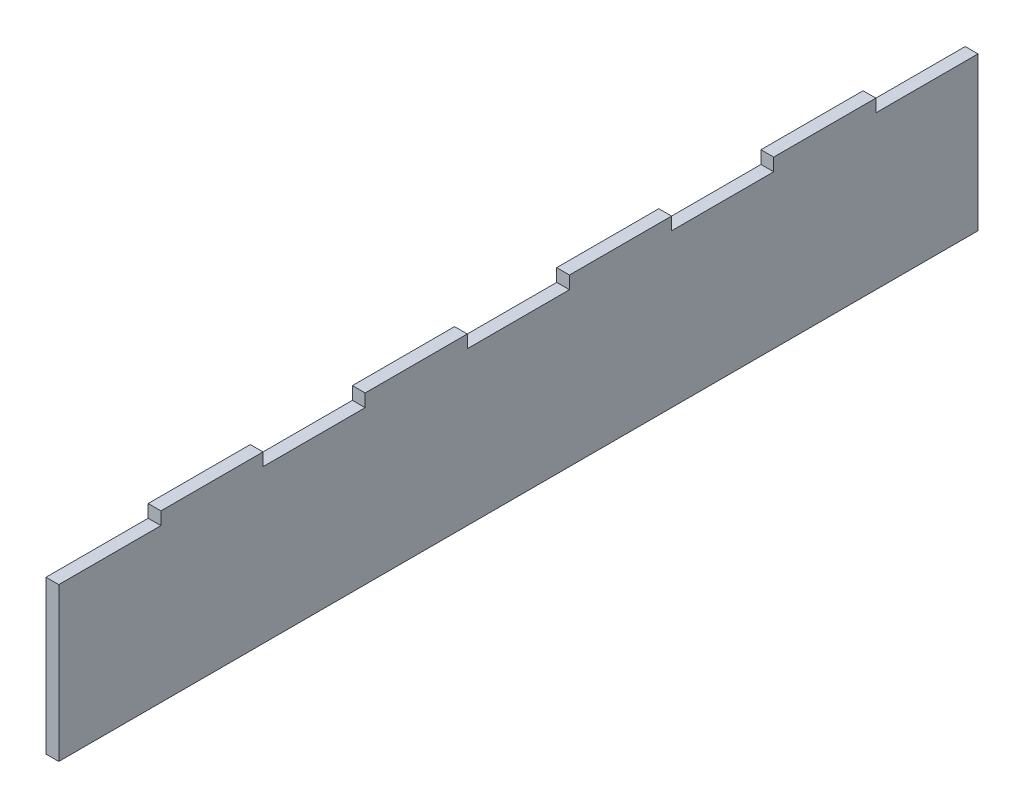
SolidWorks part; units mm, degrees
material "Pine"
ref_plane "Front Plane" through (0, 0, 0) normal (0, 0, 1) x (1, 0, 0)
ref_plane "Top Plane" through (0, 0, 0) normal (0, 1, 0) x (1, 0, 0)
ref_plane "Right Plane" through (0, 0, 0) normal (1, 0, 0) x (0, 0, -1)
sketch "Sketch1" plane through (0, 0, 0) normal (0, 0, 1) x (1, 0, 0)
  line L1 (-38.1, -38.1) -> (-44.45, -38.1)
  line L2 (-38.1, -38.1) -> (-38.1, 38.1)
  line L3 (-38.1, 38.1) -> (-44.45, 38.1)
  line L4 (-44.45, -38.1) -> (-44.45, 38.1)
extrude "Boss-Extrude1" add sketch "Sketch1" against normal up to surface (457.2 mm away)
sketch "Sketch2" plane through (0, 38.1, 0) normal (0, 1, 0) x (1, 0, 0)
  line L0 (-44.45, 457.2) -> (-44.45, 0) construction
  line L1 (-44.45, 406.4) -> (-38.1, 406.4)
  line L2 (-44.45, 406.4) -> (-44.45, 355.6)
  line L3 (-44.45, 355.6) -> (-38.1, 355.6)
  line L4 (-38.1, 406.4) -> (-38.1, 355.6)
  line L5 (-38.1, 406.4) -> (-44.45, 406.4) construction
  line L6 (-38.1, 457.2) -> (-38.1, 0) construction
  line L7 (-44.45, 355.6) -> (-38.1, 355.6) construction
  line L8 (-38.1, 203.2) -> (-44.45, 203.2) construction
  line L9 (-44.45, 304.8) -> (-38.1, 304.8)
  line L10 (-44.45, 304.8) -> (-44.45, 254)
  line L11 (-44.45, 254) -> (-38.1, 254)
  line L12 (-38.1, 304.8) -> (-38.1, 254)
  line L13 (-44.45, 203.2) -> (-38.1, 203.2)
  line L14 (-44.45, 203.2) -> (-44.45, 152.4)
  line L15 (-44.45, 152.4) -> (-38.1, 152.4)
  line L16 (-38.1, 203.2) -> (-38.1, 152.4)
  line L17 (-44.45, 152.4) -> (-38.1, 152.4) construction
  line L18 (-44.45, 50.8) -> (-38.1, 50.8) construction
  line L19 (-44.45, 101.6) -> (-38.1, 101.6)
  line L20 (-44.45, 101.6) -> (-44.45, 50.8)
  line L21 (-44.45, 50.8) -> (-38.1, 50.8)
  line L22 (-38.1, 101.6) -> (-38.1, 50.8)
  line L23 (-38.1, 101.6) -> (-44.45, 101.6) construction
  line L24 (-44.45, 254) -> (-38.1, 254) construction
  line L25 (-38.1, 304.8) -> (-44.45, 304.8) construction
extrude "Boss-Extrude2" add sketch "Sketch2" along normal up to surface (6.35 mm away)
